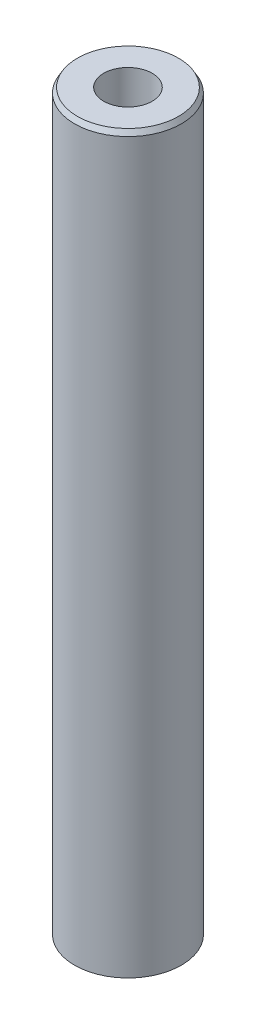
SolidWorks part; units mm, degrees
ref_plane "Front Plane" through (0, 0, 0) normal (0, 0, 1) x (1, 0, 0)
ref_plane "Top Plane" through (0, 0, 0) normal (0, 1, 0) x (1, 0, 0)
ref_plane "Right Plane" through (0, 0, 0) normal (1, 0, 0) x (0, 0, -1)
sketch "Sketch1" plane through (0, 0, 0) normal (0, 1, 0) x (1, 0, 0)
  circle A0 centre (0, 0) radius 5
  dimension "SHAFT_OD" = 10
extrude "Boss-Extrude1" add sketch "Sketch1" along normal blind 68.9585
sketch "Sketch2" plane through (0, 0, 0) normal (0, 1, 0) x (1, 0, 0)
  circle A0 centre (0, 0) radius 2.2724
  dimension "BORE_D" = 4.5448
extrude "Cut-Extrude1" cut sketch "Sketch2" along normal through all
chamfer "Chamfer1" distance 0.4669 angle 30 2 edges at (0, 68.9585, 5) (0, 0, 5) first distance on face at (0, 68.9585, 5) first distance on face at (0, 0, 2.2724)
